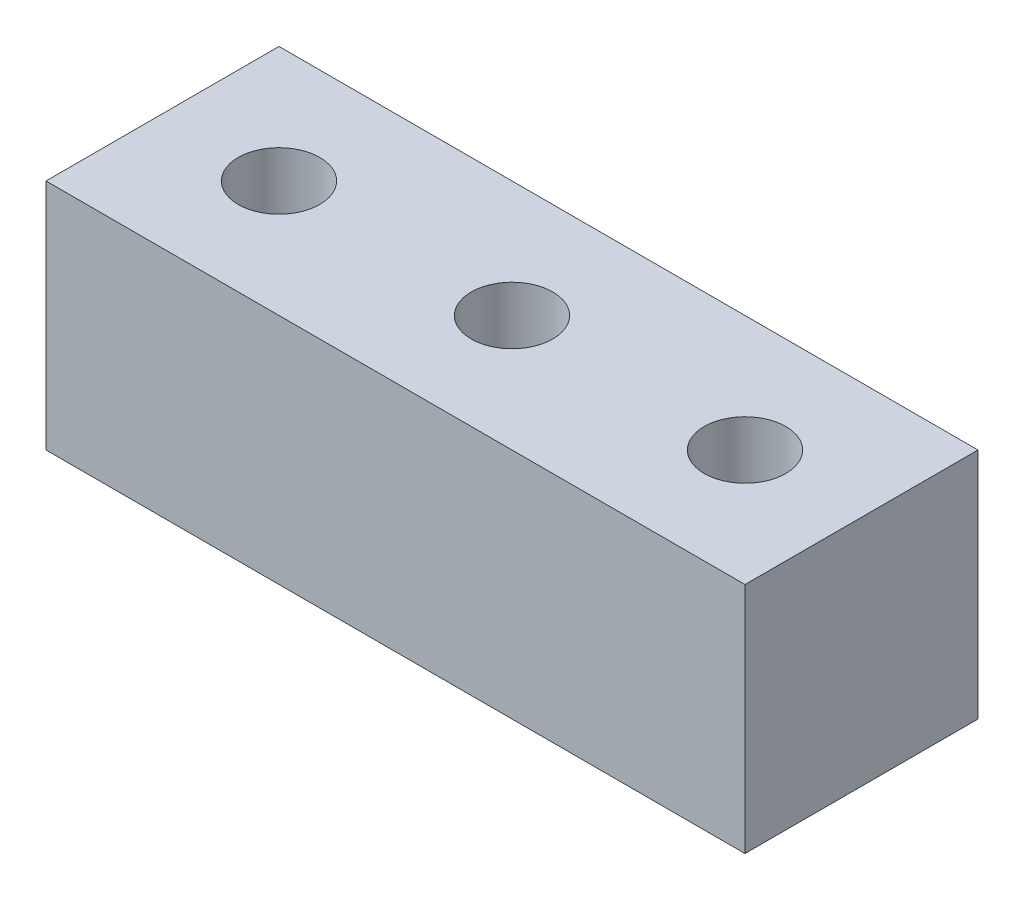
SolidWorks part; units mm, degrees
material "Custom Plastic"
ref_plane "Front Plane" through (0, 0, 0) normal (0, 0, 1) x (1, 0, 0)
ref_plane "Top Plane" through (0, 0, 0) normal (0, 1, 0) x (1, 0, 0)
ref_plane "Right Plane" through (0, 0, 0) normal (1, 0, 0) x (0, 0, -1)
sketch "Sketch1" plane through (0, 0, 0) normal (0, 1, 0) x (1, 0, 0)
  line L1 (18, -6) -> (-18, -6)
  line L2 (18, -6) -> (18, 6)
  line L3 (18, 6) -> (-18, 6)
  line L4 (-18, -6) -> (-18, 6)
  line L5 (18, -6) -> (-18, 6) construction
  line L6 (18, 6) -> (-18, -6) construction
  circle A0 centre (0, 0) radius 2.1
  circle A1 centre (-12, 0) radius 2.1
  circle A2 centre (12, 0) radius 2.1
  point P0 (0, 0)
  point P12 (0, 0)
  dimension "D3" = 4.2
  dimension "D1" = 36
  dimension "D2" = 12
  dimension "D4" = 6
  dimension "D5" = 6
extrude "Boss-Extrude1" add sketch "Sketch1" along normal blind 12
extrude "Boss-Extrude2" add sketch "Sketch1<2>" along normal blind 2 contours A1 | A0 | A2 region at (0, 0, 0) region at (-12, 0, 0) region at (12, 0, 0)
sketch "Sketch1<2>" plane through (0, 0, 0) normal (0, 1, 0) x (1, 0, 0) same geometry as "Sketch1"
